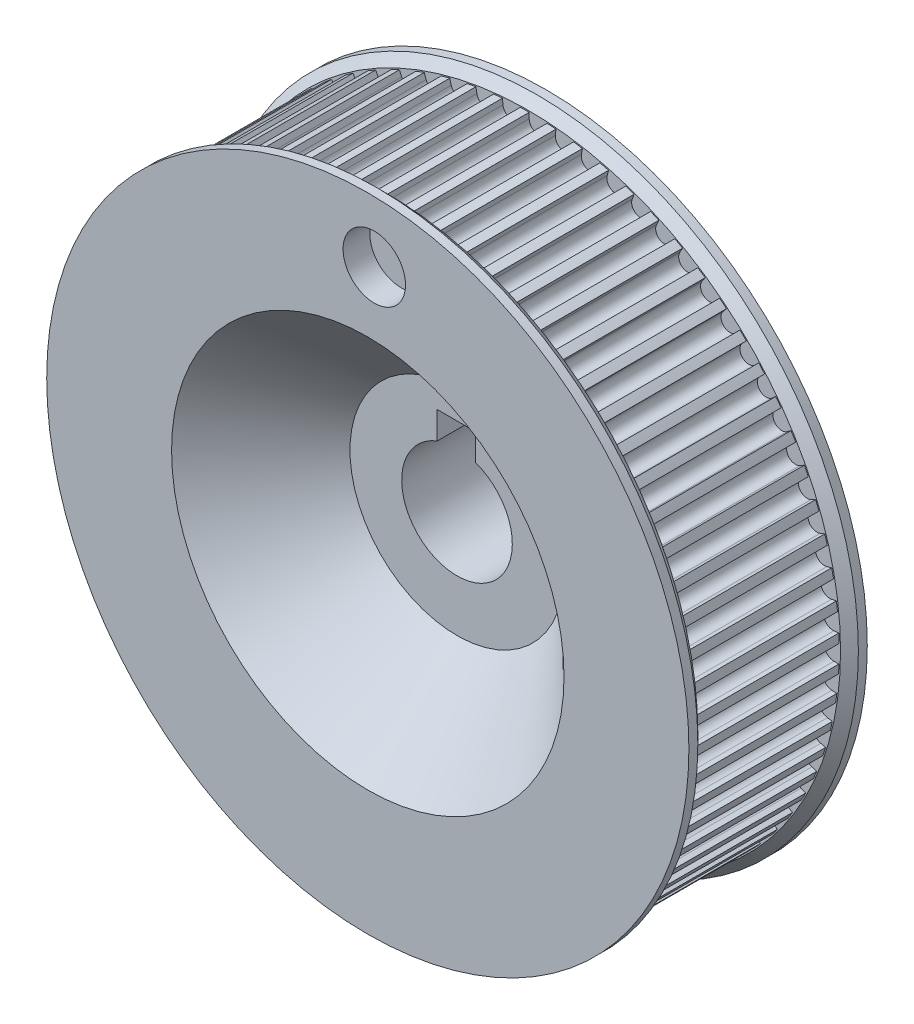
SolidWorks part; units mm, degrees
material "PA Type 6"
ref_plane "Front Plane" through (0, 0, 0) normal (0, 0, 1) x (1, 0, 0)
ref_plane "Top Plane" through (0, 0, 0) normal (0, 1, 0) x (1, 0, 0)
ref_plane "Right Plane" through (0, 0, 0) normal (1, 0, 0) x (0, 0, -1)
sketch "Sketch1" plane through (0, 0, 0) normal (0, 0, 1) x (1, 0, 0)
  circle A0 centre (0, 0) radius 12
extrude "Boss-Extrude1" add sketch "Sketch1" along normal blind 28
sketch "Sketch2" plane through (0, 0, 28) normal (0, 0, 1) x (1, 0, 0)
  circle A0 centre (0, 0) radius 6.2
extrude "Cut-Extrude1" cut sketch "Sketch2" against normal blind 60
sketch "Sketch4" plane through (0, 0, 28) normal (0, 0, 1) x (1, 0, 0)
  circle A0 centre (0, 0) radius 10
  circle A1 centre (0, 0) radius 34.85
  dimension "D1" = 69.7
extrude "Boss-Extrude2" add sketch "Sketch4" against normal blind 17
sketch "Sketch6" plane through (0, 0, 28) normal (0, 0, 1) x (1, 0, 0)
  line L0 (1.0951, 35.4896) -> (1.0951, 34.2265) construction
  line L1 (2.0951, 35.4896) -> (2.0951, 34.2265)
  line L2 (0.0951, 35.4896) -> (0.0951, 34.2265)
  arc A0 (2.0951, 35.4896) -> (0.0951, 35.4896) centre (1.0951, 35.4896) ccw
  arc A1 (0.0951, 34.2265) -> (2.0951, 34.2265) centre (1.0951, 34.2265) ccw
  point P2 (1.0951, 34.858)
  dimension "D1" = 1
extrude "Cut-Extrude3" cut sketch "Sketch6" against normal blind 18
pattern_circular "CirPattern1" count 73 over 360 about axis through (0, 0, 28) along (0, 0, 1) of "Cut-Extrude3"
sketch "Sketch7" plane through (0, 0, 28) normal (0, 0, 1) x (1, 0, 0)
  circle A0 centre (0, 0) radius 7
  circle A1 centre (0, 0) radius 36
extrude "Boss-Extrude3" add sketch "Sketch7" along normal blind 2
pattern_linear "LPattern1" count 2 spacing 18 along (0, 0, -1) of "Boss-Extrude3"
chamfer "Chamfer1" distance 1 angle 45 2 edges at (36, 0, 28) (36, 0, 12)
sketch "Sketch5" plane through (0, 0, 28) normal (0, 0, 1) x (1, 0, 0)
  circle A0 centre (0.7243, 29.1419) radius 3.5
extrude "Cut-Extrude2" cut sketch "Sketch5" against normal blind 1 and the other way blind 10
sketch "Sketch8" plane through (0, 0, 0) normal (0, 0, -1) x (-1, 0, 0)
  line L1 (-2.0807, 8.8431) -> (2.2164, 8.8431)
  line L2 (-2.0807, 8.8431) -> (-2.0807, 5.4054)
  line L3 (-2.0807, 5.4054) -> (2.2164, 5.4054)
  line L4 (2.2164, 8.8431) -> (2.2164, 5.4054)
extrude "Cut-Extrude4" cut sketch "Sketch8" against normal blind 100
sketch "Sketch9" plane through (0, 0, 30) normal (0, 0, 1) x (1, 0, 0)
  circle A0 centre (0, 0) radius 12
  circle A1 centre (0, 0) radius 36 construction
extrude "Cut-Extrude5" cut sketch "Sketch9" against normal blind 10
chamfer "Chamfer2" distance 10 angle 45 1 edges at (12, 0, 30)
chamfer "Chamfer3" distance 2 angle 45 1 edges at (12, 0, 10)
chamfer "Chamfer4" distance 1 angle 45 1 edges at (0.0723, -6.1996, 0)
chamfer "Chamfer5" distance 1 angle 45 1 edges at (12, 0, 0)
sketch "Sketch10" plane through (0, 0, 10) normal (0, 0, -1) x (-1, 0, 0)
  circle A0 centre (1.5511, 24.7694) radius 7
extrude "Cut-Extrude6" cut sketch "Sketch10" against normal blind 15
fillet "Fillet1" radius 2 1 edges at (-8.5511, 24.7694, 10)
pattern_circular "CirPattern2" count 8 over 360 about axis through (0, 0, 10) along (0, 0, 1) of "Fillet1", "Cut-Extrude6"
